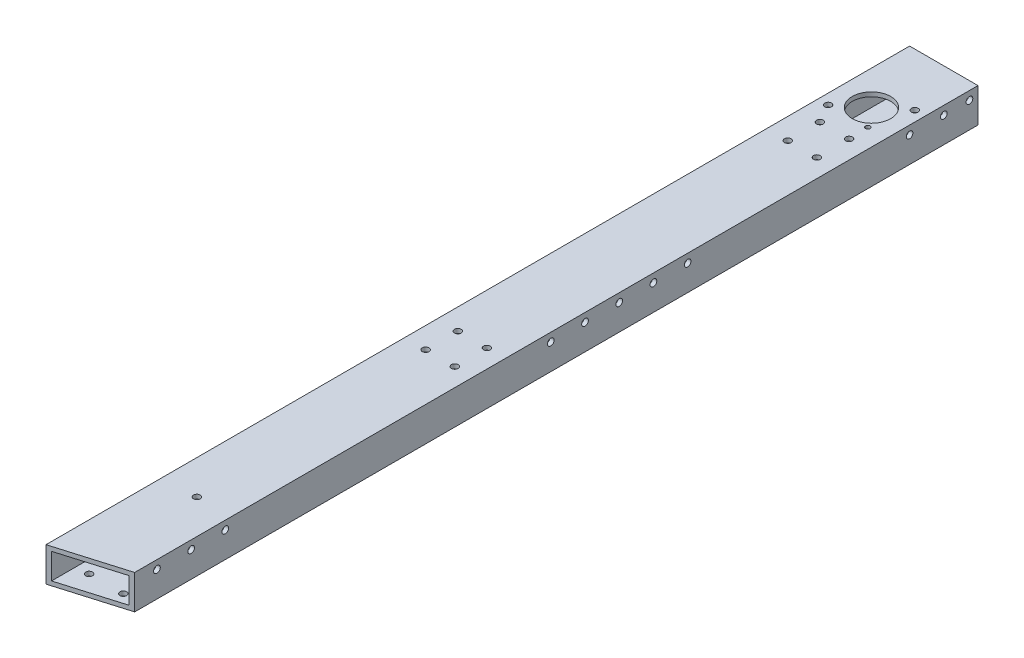
SolidWorks part; units mm, degrees
ref_plane "Front Plane" through (0, 0, 0) normal (0, 0, 1) x (1, 0, 0)
ref_plane "Top Plane" through (0, 0, 0) normal (0, 1, 0) x (1, 0, 0)
ref_plane "Right Plane" through (0, 0, 0) normal (1, 0, 0) x (0, 0, -1)
sketch "Sketch1" plane through (0, 0, 0) normal (0, 0, 1) x (1, 0, 0)
  line L0 (-22.225, 9.525) -> (22.225, 9.525)
  line L2 (-25.4, 12.7) -> (25.4, 12.7)
  line L3 (-25.4, 12.7) -> (-25.4, -12.7)
  line L4 (-25.4, -12.7) -> (25.4, -12.7)
  line L5 (25.4, 12.7) -> (25.4, -12.7)
  line L10 (22.225, 9.525) -> (22.225, -9.525)
  line L11 (-22.225, -9.525) -> (22.225, -9.525)
  line L12 (-22.225, 9.525) -> (-22.225, -9.525)
  point P12 (0, 12.7)
  point P14 (25.4, 0)
  dimension "Wall Thickness" = 3.175
  dimension "Outside Width" = 50.8
  dimension "Outside Height" = 25.4
  dimension "Inside Height" = 19.05
  dimension "Inside Width" = 44.45
sketch "Sketch2" plane through (0, 0, 0) normal (1, 0, 0) x (0, 0, -1)
  line L0 (320.675, 0) -> (-320.675, 0)
  point P4 (0, 0)
  point P7 (-320.675, 0)
  point P10 (320.675, 0)
  dimension "Length" = 641.35
sketch "Sketch3" plane through (0, 0, 0) normal (0, 0, 1) x (1, 0, 0)
  line L21 (25.4, 12.7) -> (-25.4, 12.7)
  line L22 (25.4, -12.7) -> (25.4, 12.7)
  line L23 (-25.4, -12.7) -> (25.4, -12.7)
  line L24 (-25.4, 12.7) -> (-25.4, -12.7)
  line L25 (25.4, 12.7) -> (-25.4, 12.7)
  line L26 (25.4, -12.7) -> (25.4, 12.7)
  line L27 (-25.4, -12.7) -> (25.4, -12.7)
  line L28 (-25.4, 12.7) -> (-25.4, -12.7)
  line L29 (22.225, 9.525) -> (-22.225, 9.525)
  line L30 (22.225, -9.525) -> (22.225, 9.525)
  line L31 (-22.225, -9.525) -> (22.225, -9.525)
  line L32 (-22.225, 9.525) -> (-22.225, -9.525)
  line L33 (22.225, 9.525) -> (-22.225, 9.525)
  line L34 (22.225, -9.525) -> (22.225, 9.525)
  line L35 (-22.225, -9.525) -> (22.225, -9.525)
  line L36 (-22.225, 9.525) -> (-22.225, -9.525)
  dimension "D1" = 0
  dimension "D2" = 0
extrude "Boss-Extrude1" add sketch "Sketch3" along normal up to vertex (320.675 mm away) and the other way up to vertex (320.675 mm away) up to point (0, 0, 320.675) other way up to point (0, 0, -320.675)
sketch "Drawing Reference" plane through (0, 0, 0) normal (1, 0, 0) x (0, 0, -1)
  line L0 (-320.675, 0) -> (320.675, 0) construction
  line L1 (0, -12.7) -> (0, 12.7) construction
  line L2 (-320.675, -12.7) -> (320.675, -12.7) construction
  line L5 (-320.675, 12.7) -> (320.675, 12.7) construction
  point P7 (-284.099, 0)
  point P8 (284.099, 0)
  dimension "D1" = 36.576
sketch "Sketch4" plane through (0, 12.7, 0) normal (0, 1, 0) x (1, 0, 0)
  line L0 (-25.4, -320.675) -> (25.4, -305.6274)
  line L1 (25.4, -320.675) -> (25.4, 320.675) construction
  line L2 (25.4, -320.675) -> (-25.4, -320.675)
  dimension "D1" = 16.5
extrude "Cut-Extrude1" cut sketch "Sketch4" against normal through all and the other way through all flip side to cut
sketch "Sketch8" plane through (0, 12.7, 0) normal (0, 1, 0) x (1, 0, 0)
  line L0 (0, 320.675) -> (0, 266.954) construction
  line L1 (25.4, 320.675) -> (-25.4, 320.675) construction
  circle A0 centre (0, 266.954) radius 14.2875
  dimension "D1" = 53.721
extrude "Cut-Extrude2" cut sketch "Sketch8" against normal through all
sketch "Sketch9" plane through (0, -12.7, 0) normal (0, -1, 0) x (1, 0, 0)
  line L0 (-12.7762, 284.753) -> (-12.7762, 301.263) construction
  line L1 (-12.7762, 301.263) -> (12.6238, 301.263) construction
  line L2 (12.6238, 301.263) -> (12.6238, 284.753) construction
  line L3 (12.6238, 284.753) -> (-12.7762, 284.753) construction
hole_wizard "#10 Clearance Hole1" positions "Sketch10" profile "Sketch11" hole size "#10" standard "ANSI Inch"
sketch "Sketch10" plane through (0, -12.7, 0) normal (0, -1, 0) x (-1, 0, 0)
  point P0 (-12.6238, -284.753)
  point P3 (12.7762, -284.753)
  point P6 (12.7762, -301.263)
  point P9 (-12.6238, -301.263)
sketch "Sketch11" plane through (12.6238, -12.7, 284.753) normal (1, 0, 0) x (0, 0, -1)
  line L0 (0, 0) -> (0, 6.5757)
  line L1 (0, 6.5757) -> (2.4892, 5.08)
  line L2 (2.4892, 5.08) -> (2.4892, 0)
  line L5 (2.4892, 0) -> (0, 0)
  line L10 (0, 6.5757) -> (-2.4892, 5.08) construction
  line L11 (0, -6.35) -> (0, 107.95) construction
  dimension "Hole Dia." = 4.9784
  dimension "Hole Depth" = 5.08
  dimension "Drill Angle" = 118
sketch "Sketch12" plane through (25.4, 0, 0) normal (1, 0, 0) x (0, 0, -1)
  line L0 (320.675, 533.4) -> (-305.6274, 533.4) construction
  line L1 (320.675, 520.7) -> (320.675, 546.1) construction
  line L2 (-305.6274, 546.1) -> (-305.6274, 520.7) construction
hole_wizard "#10 Clearance Hole2" positions "Sketch13" profile "Sketch14" hole size "#10" standard "ANSI Inch" end condition through all
sketch "Sketch13" plane through (25.4, 0, 0) normal (1, 0, 0) x (0, 0, -1)
  point P0 (314.325, 6.35)
  point P3 (295.275, 6.35)
sketch "Sketch14" plane through (25.4, 6.35, -314.325) normal (0, 1, 0) x (0, 0, -1)
  line L0 (0, 0) -> (0, 50.8)
  line L1 (0, 50.8) -> (2.4892, 50.8)
  line L2 (2.4892, 50.8) -> (2.4892, 0)
  line L5 (2.4892, 0) -> (0, 0)
  line L11 (0, -6.35) -> (0, 107.95) construction
  dimension "Thru Hole Dia." = 4.9784
  dimension "Thru Hole Depth" = 50.8
hole_wizard "#10 Clearance Hole3" positions "Sketch15" profile "Sketch16" hole size "#10" standard "ANSI Inch" end condition through all
sketch "Sketch15" plane through (25.4, 0, 0) normal (1, 0, 0) x (0, 0, -1)
  point P0 (105.029, 6.35)
  point P3 (79.629, 6.35)
  point P6 (54.229, 6.35)
  point P9 (28.829, 6.35)
  point P12 (3.429, 6.35)
  point P24 (-289.0885, 6.3882)
  point P27 (-263.6885, 6.3882)
  point P30 (-238.3267, 6.3882)
sketch "Sketch16" plane through (25.4, 6.35, -105.029) normal (0, 1, 0) x (0, 0, -1)
  line L0 (0, 0) -> (0, 50.8)
  line L1 (0, 50.8) -> (2.4892, 50.8)
  line L2 (2.4892, 50.8) -> (2.4892, 0)
  line L5 (2.4892, 0) -> (0, 0)
  line L11 (0, -6.35) -> (0, 107.95) construction
  dimension "Thru Hole Dia." = 4.9784
  dimension "Thru Hole Depth" = 50.8
sketch "Sketch18" plane through (0, 12.7, 0) normal (0, 1, 0) x (1, 0, 0)
  line L0 (-17.786, 252.537) -> (17.786, 281.371) construction
  line L1 (0, 266.954) -> (11.3559, 252.9444) construction
hole_wizard "#10 Clearance Hole4" positions "Sketch19" profile "Sketch20" hole size "#10" standard "ANSI Inch"
sketch "Sketch19" plane through (0, 12.7, 0) normal (0, 1, 0) x (1, 0, 0)
  point P0 (17.786, 281.371)
  point P3 (-17.786, 252.537)
sketch "Sketch20" plane through (17.786, 12.7, -281.371) normal (1, 0, 0) x (0, 0, 1)
  line L0 (0, 0) -> (0, 6.5757)
  line L1 (0, 6.5757) -> (2.4892, 5.08)
  line L2 (2.4892, 5.08) -> (2.4892, 0)
  line L5 (2.4892, 0) -> (0, 0)
  line L10 (0, 6.5757) -> (-2.4892, 5.08) construction
  line L11 (0, -6.35) -> (0, 107.95) construction
  dimension "Hole Dia." = 4.9784
  dimension "Hole Depth" = 5.08
  dimension "Drill Angle" = 118
sketch "Sketch21" plane through (0, 12.7, 0) normal (0, 1, 0) x (1, 0, 0)
  line L0 (-0.0762, -284.753) -> (-0.0762, -233.953) construction
  line L1 (12.6238, -284.753) -> (-12.7762, -284.753) construction
  dimension "D1" = 50.8
hole_wizard "#10 Clearance Hole5" positions "Sketch22" profile "Sketch23" hole size "#10" standard "ANSI Inch" end condition through all
sketch "Sketch22" plane through (0, 12.7, 0) normal (0, 1, 0) x (1, 0, 0)
  point P0 (-0.0762, -233.953)
sketch "Sketch23" plane through (-0.0762, 12.7, 233.953) normal (1, 0, 0) x (0, 0, 1)
  line L0 (0, 0) -> (0, 25.4)
  line L1 (0, 25.4) -> (2.4892, 25.4)
  line L2 (2.4892, 25.4) -> (2.4892, 0)
  line L5 (2.4892, 0) -> (0, 0)
  line L11 (0, -6.35) -> (0, 107.95) construction
  dimension "Thru Hole Dia." = 4.9784
  dimension "Thru Hole Depth" = 25.4
hole_wizard "Tap Drill for #8-32 Tap1" positions "Sketch24" profile "Sketch25" hole size "#8-32" standard "ANSI Inch"
sketch "Sketch24" plane through (0, 12.7, 0) normal (0, 1, 0) x (1, 0, 0)
  point P0 (11.3559, 252.9444)
sketch "Sketch25" plane through (11.3559, 12.7, -252.9444) normal (1, 0, 0) x (0, 0, 1)
  line L0 (0, 0) -> (0, 6.1178)
  line L1 (0, 6.1178) -> (1.7272, 5.08)
  line L2 (1.7272, 5.08) -> (1.7272, 0)
  line L5 (1.7272, 0) -> (0, 0)
  line L10 (0, 6.1178) -> (-1.7272, 5.08) construction
  line L11 (0, -6.35) -> (0, 107.95) construction
  dimension "Hole Dia." = 3.4544
  dimension "Hole Depth" = 5.08
  dimension "Drill Angle" = 118
hole_wizard "#10 Clearance Hole6" positions "Sketch26" profile "Sketch27" hole size "#10" standard "ANSI Inch" end condition through all
sketch "Sketch26" plane through (0, 12.7, 0) normal (0, 1, 0) x (1, 0, 0)
  point P0 (-9.7957, 238.4742)
  point P3 (11.8451, 238.4742)
  point P6 (11.8451, 214.5982)
  point P9 (-9.7957, 214.5982)
  point P12 (11.8451, -30.4483)
  point P15 (-9.7957, -30.4483)
  point P18 (-9.7957, -54.3243)
  point P21 (11.8451, -54.3243)
sketch "Sketch27" plane through (-9.7957, 12.7, -238.4742) normal (1, 0, 0) x (0, 0, 1)
  line L0 (0, 0) -> (0, 25.4)
  line L1 (0, 25.4) -> (5.2197, 25.4)
  line L2 (2.4892, 22.2589) -> (2.4892, 0)
  line L5 (2.4892, 0) -> (0, 0)
  line L7 (5.2197, 25.4) -> (2.4892, 22.2589)
  line L8 (-5.2197, 25.4) -> (-2.4892, 22.2589) construction
  line L11 (0, -6.35) -> (0, 107.95) construction
  dimension "Thru Hole Dia." = 4.9784
  dimension "Thru Hole Depth" = 25.4
  dimension "Far C'Sink Dia." = 10.4394
  dimension "Far C'Sink Angle" = 82
hole_wizard "#10 (0.1935) Diameter Hole1" positions "Sketch28" profile "Sketch29" hole size "#10" standard "ANSI Inch"
sketch "Sketch28" plane through (25.4, 0, 0) normal (1, 0, 0) x (0, 0, -1)
  point P5 (269.875, 6.35)
sketch "Sketch29" plane through (25.4, 6.35, -269.875) normal (0, 1, 0) x (0, 0, -1)
  line L0 (0, 0) -> (0, 4.7786)
  line L1 (0, 4.7786) -> (2.4574, 3.302)
  line L2 (2.4574, 3.302) -> (2.4574, 0)
  line L5 (2.4574, 0) -> (0, 0)
  line L10 (0, 4.7786) -> (-2.4574, 3.302) construction
  line L11 (0, -6.35) -> (0, 107.95) construction
  dimension "Hole Dia." = 4.9149
  dimension "Hole Depth" = 3.302
  dimension "Drill Angle" = 118
equation "\"D1@Drawing Reference\"=\"Outside Width@Sketch1\" * 0.72"
